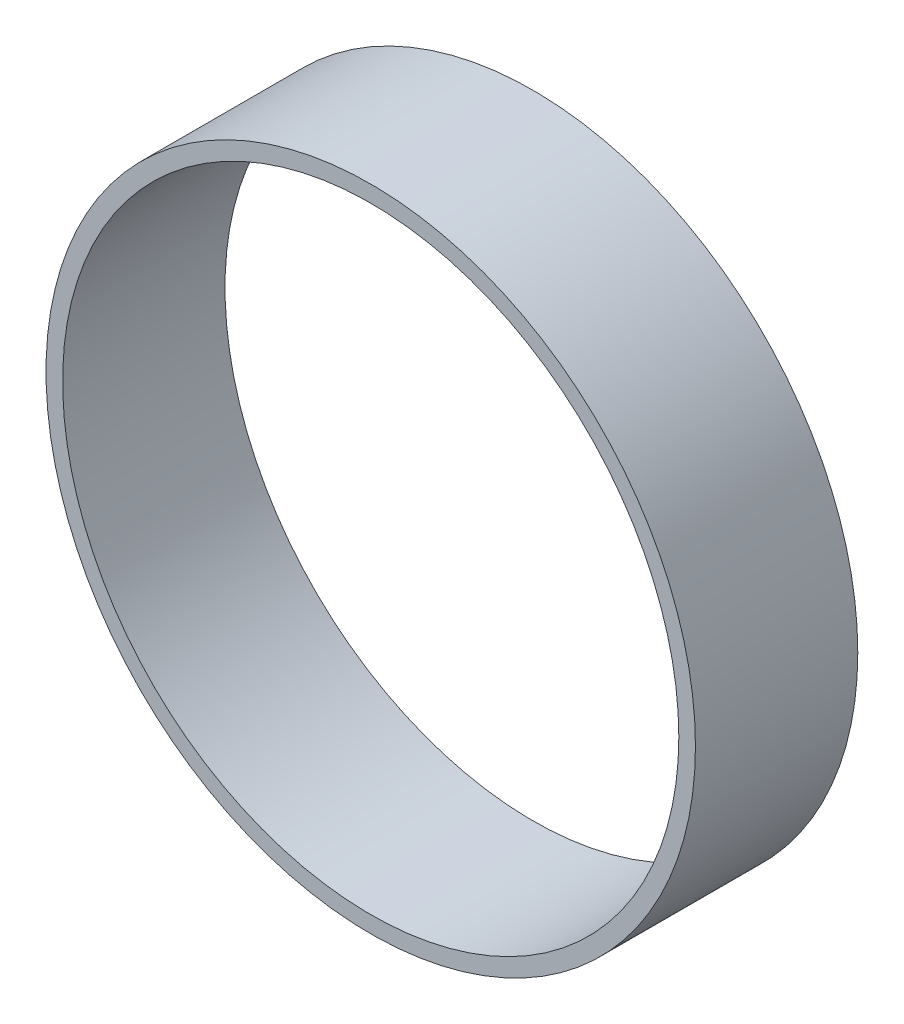
SolidWorks part; units mm, degrees
ref_plane "Front Plane" through (0, 0, 0) normal (0, 0, 1) x (1, 0, 0)
ref_plane "Top Plane" through (0, 0, 0) normal (0, 1, 0) x (1, 0, 0)
ref_plane "Right Plane" through (0, 0, 0) normal (1, 0, 0) x (0, 0, -1)
sketch "Sketch1" plane through (0, 0, 0) normal (0, 0, 1) x (1, 0, 0)
  circle A0 centre (0, 0) radius 48.2
  circle A1 centre (0, 0) radius 50.8
  dimension "Out_dia" = 101.6
  dimension "Thickness" = 2.6
extrude "BaseSection" add sketch "Sketch1" along normal mid plane 25.4
